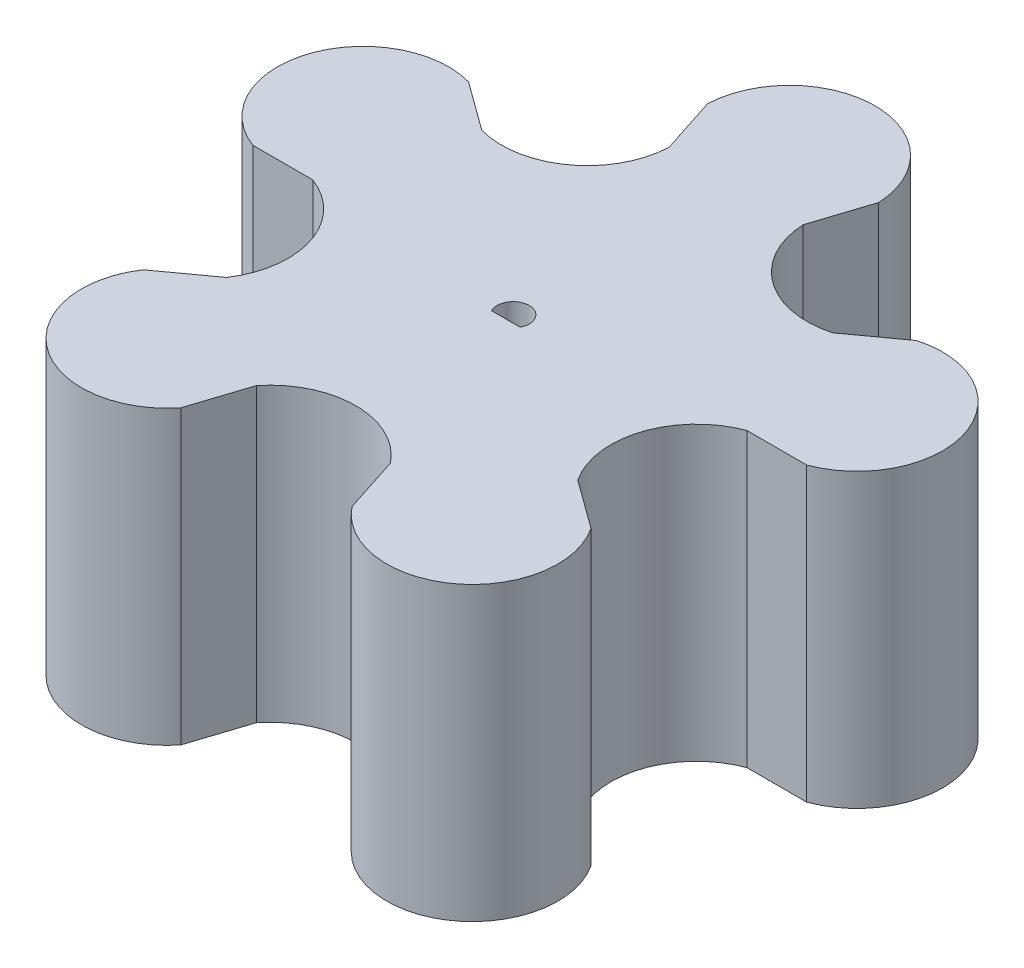
SolidWorks part; units mm, degrees
ref_plane "Front Plane" through (0, 0, 0) normal (0, 0, 1) x (1, 0, 0)
ref_plane "Top Plane" through (0, 0, 0) normal (0, 1, 0) x (1, 0, 0)
ref_plane "Right Plane" through (0, 0, 0) normal (1, 0, 0) x (0, 0, -1)
sketch "Sketch2" plane through (0, 0, 0) normal (0, 1, 0) x (1, 0, 0)
  line L0 (0, 0) -> (0, 16.9342) construction
  line L1 (-5.5828, 34.124) -> (-4.3753, 30.4076)
  line L2 (-4.3753, 30.4076) -> (-4.3565, 30.3846)
  line L3 (-14.616, 6.3226) -> (-11.4547, 8.6195)
  line L4 (-18.0664, 16.9418) -> (-14.1588, 16.9418)
  line L5 (-14.616, 27.561) -> (-11.4547, 25.2641)
  line L6 (5.5828, 34.124) -> (4.3753, 30.4076)
  line L7 (14.616, 27.561) -> (11.4547, 25.2641)
  line L8 (18.0664, 16.9418) -> (14.1588, 16.9418)
  line L9 (14.1588, 16.9418) -> (14.1782, 17.0613)
  line L10 (14.616, 6.3226) -> (11.4547, 8.6195)
  line L11 (11.4547, 8.6195) -> (11.6097, 8.7137)
  line L12 (5.5828, -0.2404) -> (4.3753, 3.476)
  line L13 (-5.5828, -0.2404) -> (-4.3753, 3.476)
  circle A0 centre (0, 16.9342) radius 16.9442 construction
  arc A1 (-14.616, 6.3226) -> (-5.5828, -0.2404) centre (-9.9581, 3.2356) ccw
  arc A3 (-14.616, 27.561) -> (-18.0664, 16.9418) centre (-16.1126, 22.1771) ccw
  arc A7 (18.0664, 16.9418) -> (14.616, 27.561) centre (16.1126, 22.1771) ccw
  arc A9 (5.5828, -0.2404) -> (14.616, 6.3226) centre (9.9581, 3.2356) ccw
  arc A10 (-11.4547, 25.2641) -> (-4.3753, 30.4076) centre (-9.9581, 30.648) ccw
  arc A12 (-11.4547, 8.6195) -> (-14.1588, 16.9418) centre (-16.1126, 11.7065) ccw
  arc A14 (4.3753, 3.476) -> (-4.3753, 3.476) centre (0, 0) ccw
  arc A16 (14.1588, 16.9418) -> (11.4547, 8.6195) centre (16.1126, 11.7065) ccw
  arc A18 (5.5828, 34.124) -> (-5.5828, 34.124) centre (0, 33.8836) ccw
  arc A19 (4.3753, 30.4076) -> (11.4547, 25.2641) centre (9.9581, 30.648) ccw
  point P25 (0, 16.9418)
extrude "Boss-Extrude1" add sketch "Sketch2" along normal blind 19.05 contours A19 L6 A18 L1 A10 L5 A3 L4 A12 L3 A1 L13 A14 L12 A9 L10 A16 L8 A7 L7 region at (0, 0, -16.9418)
sketch "Sketch3" plane through (0, 19.05, 0) normal (0, 1, 0) x (1, 0, 0)
  line L0 (0, 5.588) -> (10.7981, 13.4333) construction
  line L1 (10.9624, 13.8748) -> (6.6736, 26.1272) construction
  line L2 (6.6736, 26.1272) -> (-6.6736, 26.1272) construction
  line L3 (-6.6736, 26.1272) -> (-10.7981, 13.4333) construction
  line L4 (-10.7981, 13.4333) -> (0, 5.588) construction
  line L5 (0, 26.1272) -> (0, 5.588) construction
  line L6 (0, 16.9054) -> (0, 15.3814) construction
  line L7 (-0.9333, 15.3814) -> (0.9333, 15.3814)
  arc A0 (0.9333, 15.3814) -> (-0.9333, 15.3814) centre (0, 15.8576) ccw
  arc A15 (4.3753, 3.476) -> (-4.3753, 3.476) centre (0, 0) ccw construction
  arc A16 (14.1588, 16.9418) -> (11.4547, 8.6195) centre (16.1126, 11.7065) ccw construction
  arc A17 (4.3753, 30.4076) -> (11.4547, 25.2641) centre (9.9581, 30.648) ccw construction
  arc A18 (-11.4547, 25.2641) -> (-4.3753, 30.4076) centre (-9.9581, 30.648) ccw construction
  arc A19 (-11.4547, 8.6195) -> (-14.1588, 16.9418) centre (-16.1126, 11.7065) ccw construction
extrude "Cut-Extrude1" cut sketch "Sketch3" against normal through all
sketch "Sketch4" plane through (0, 19.05, 0) normal (0, 1, 0) x (1, 0, 0)
  circle A0 centre (0, 15.8576) radius 18.7242 construction
